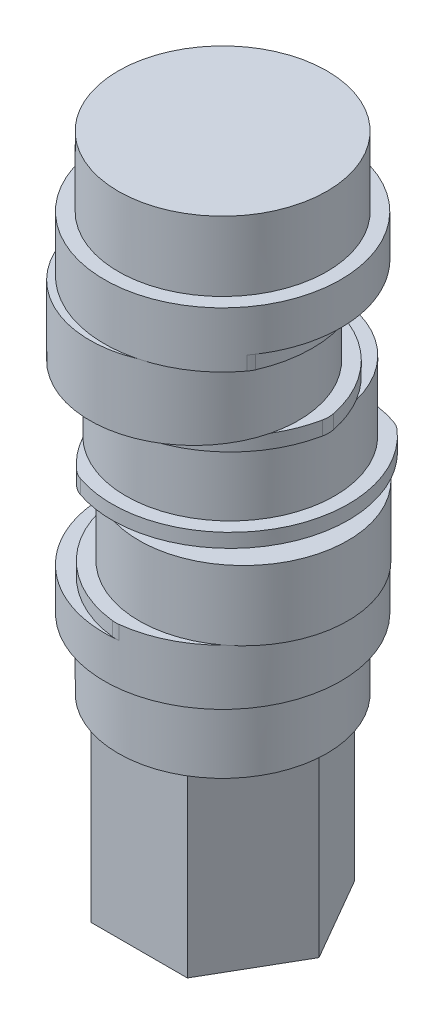
SolidWorks part; units mm, degrees
ref_plane "Front Plane" through (0, 0, 0) normal (0, 0, 1) x (1, 0, 0)
ref_plane "Top Plane" through (0, 0, 0) normal (0, 1, 0) x (1, 0, 0)
ref_plane "Right Plane" through (0, 0, 0) normal (1, 0, 0) x (0, 0, -1)
sketch "Sketch3" plane through (0, 0, 0) normal (0, 1, 0) x (1, 0, 0)
  line L0 (-0.75, 1.299) -> (0, 0) construction
  line L1 (0, 0) -> (-0.75, -1.299) construction
  line L2 (0, 0) -> (1.5, 0) construction
  circle A0 centre (0, 0) radius 1.5 construction
  circle A1 centre (1.5, 0) radius 8.5
  circle A2 centre (-0.75, 1.299) radius 8.5
  circle A3 centre (-0.75, -1.299) radius 8.5
  dimension "D1" = 3
  dimension "D2" = 17
  dimension "D3" = 120
  dimension "D4" = 120
sketch "Sketch4" plane through (0, 0, 0) normal (0, 1, 0) x (1, 0, 0)
  line L1 (-3.4641, 6) -> (-6.9282, 0)
  line L2 (-6.9282, 0) -> (-3.4641, -6)
  line L3 (-3.4641, -6) -> (3.4641, -6)
  line L4 (3.4641, -6) -> (6.9282, 0)
  line L5 (6.9282, 0) -> (3.4641, 6)
  line L6 (3.4641, 6) -> (-3.4641, 6)
  circle A0 centre (0, 0) radius 6 construction
  dimension "D1" = 12
extrude "Boss-Extrude1" add sketch "Sketch4" along normal blind 13
sketch "Sketch5" plane through (0, 13, 0) normal (0, 1, 0) x (1, 0, 0)
  circle A0 centre (0, 0) radius 7.5
  dimension "D1" = 15
extrude "Boss-Extrude2" add sketch "Sketch5" along normal blind 8
sketch "Sketch6" plane through (0, 21, 0) normal (0, 1, 0) x (1, 0, 0)
  circle A0 centre (0, 0) radius 8.5
  circle A1 centre (1.5, 0) radius 8.5
  circle M1 centre (0, 0) radius 7.5
  dimension "D1" = 17
extrude "Boss-Extrude3" add sketch "Sketch6" along normal blind 1 contours A1 M1 | A0 A1 M1 region at (6.1121, 21, 5.5946) region at (0.1719, 21, 0)
sketch "Sketch7" plane through (0, 22, 0) normal (0, 1, 0) x (1, 0, 0)
  circle A0 centre (1.5, 0) radius 7.5
  arc A1 (-4.5833, 5.9366) -> (-4.5833, -5.9366) centre (0, 0) ccw construction
extrude "Boss-Extrude4" add sketch "Sketch7" along normal blind 5
sketch "Sketch8" plane through (0, 27, 0) normal (0, 1, 0) x (1, 0, 0)
  circle A0 centre (1.5, 0) radius 8.5
  circle A1 centre (-0.75, 1.299) radius 8.5
  circle A2 centre (1.5, 0) radius 8.5 construction
  circle M1 centre (1.5, 0) radius 7.5
extrude "Boss-Extrude5" add sketch "Sketch8" along normal blind 1 contours A1 M1 | A1 A0 M1 region at (5.5922, 27, -6.6403) region at (0.8921, 27, -0.3509)
sketch "Sketch9" plane through (0, 28, 0) normal (0, 1, 0) x (1, 0, 0)
  circle A0 centre (-0.75, 1.299) radius 7.5
  arc A1 (-0.6012, -7.1997) -> (6.6845, 5.4195) centre (1.5, 0) ccw construction
extrude "Boss-Extrude6" add sketch "Sketch9" along normal blind 5
sketch "Sketch11" plane through (0, 33, 0) normal (0, 1, 0) x (1, 0, 0)
  circle A0 centre (-0.75, 1.299) radius 8.5
  circle A1 centre (-0.75, -1.299) radius 8.5
  arc A2 (-3.8251, -6.6252) -> (4.5751, 7.9243) centre (-0.75, 1.299) ccw construction
  circle M1 centre (-0.75, 1.299) radius 7.5
extrude "Boss-Extrude7" add sketch "Sketch11" along normal blind 1 contours A1 M1 | A0 A1 M1 region at (-8.5574, 33, -1.5267) region at (-0.75, 33, -0.5972)
sketch "Sketch12" plane through (0, 34, 0) normal (0, 1, 0) x (1, 0, 0)
  circle A0 centre (-0.75, -1.299) radius 7.5
  arc A1 (6.5357, 3.0792) -> (-8.0357, 3.0792) centre (-0.75, 1.299) ccw construction
extrude "Boss-Extrude8" add sketch "Sketch12" along normal blind 5
sketch "Sketch13" plane through (0, 39, 0) normal (0, 1, 0) x (1, 0, 0)
  circle A0 centre (-0.75, -1.299) radius 8.5
  circle A1 centre (0, 0) radius 8.5
  arc A3 (7.6501, 0) -> (-9.1501, 0) centre (-0.75, -1.299) ccw construction
  circle M1 centre (-0.75, -1.299) radius 7.5
extrude "Boss-Extrude9" add sketch "Sketch13" along normal blind 1 contours A1 M1 | A1 A0 M1 region at (7.3307, 39, 3.0859) region at (-0.664, 39, 1.1501)
sketch "Sketch14" plane through (0, 40, 0) normal (0, 1, 0) x (1, 0, 0)
  circle A0 centre (0, 0) radius 7.5
  arc A1 (6.5357, 3.0792) -> (-8.0357, 3.0792) centre (-0.75, 1.299) ccw construction
extrude "Boss-Extrude10" add sketch "Sketch14" along normal blind 8
fillet "Fillet1" radius 2 8 edges at (0.75, 21.5, -8.4668) (0.75, 21.5, 8.4668) (-3.8251, 27.5, 6.6252) (4.5751, 27.5, -7.9243) (7.6501, 33.5, 0) (-9.1501, 33.5, 0) (-7.7075, 39.5, -3.5839) (6.9575, 39.5, 4.8829)
sketch "Sketch15" plane through (0, 21, 0) normal (0, -1, 0) x (1, 0, 0)
  circle A0 centre (0, 0) radius 8.5
  dimension "D1" = 17
extrude "Boss-Extrude11" add sketch "Sketch15" along normal blind 3
sketch "Sketch16" plane through (0, 40, 0) normal (0, -1, 0) x (1, 0, 0)
  circle A0 centre (0, 0) radius 8.5
  dimension "D1" = 17
extrude "Boss-Extrude12" add sketch "Sketch16" against normal blind 3
equation "\"N_pin\"= 24"
equation "\"R_pin\"= 60"
equation "\"d_pin\"= 13"
equation "\"e\"= 1.5"
equation "\"t_disk\"= 5"
equation "\"N_outpin\"= 8"
equation "\"R_outpin\"= 34"
equation "\"d_outpin\"= 13"
equation "\"N_lobes\"= \"N_pin\" - 1"
equation "\"d_outhole\"= \"d_outpin\" + 2 * \"e\""
equation "\"ratio\"= \"N_lobes\""
equation "\"d_center\"= 24"
equation "\"a_hole1\"= 0 / \"N_lobes\""
equation "\"a_hole2\"= 360 / \"N_disk\" / \"N_lobes\""
equation "\"a_hole3\"= 720 / \"N_disk\" / \"N_lobes\""
equation "\"N_disk\"= 3"
equation "\"t_gap\"= 1"
equation "\"L_stack\"= \"N_disk\" * \"t_disk\" + (\"N_disk\" - 1) * \"t_gap\""
equation "\"d_pinshaft\"= 6"
equation "\"d_ecc\"= 15"
equation "\"d_outbrg\"= 47"
equation "\"w_outbrg\"= 7"
equation "\"d_outshaft\"= 35"
equation "\"w_brg\"= 5"
equation "\"D1@Boss-Extrude5\"=\"t_gap\""
equation "\"D1@Boss-Extrude7\"=\"t_gap\""
equation "\"c_run\"= 0.5"
equation "\"c_ax\"= \"t_gap\""
equation "\"D_pocket\"= 2 * \"R_pin\" + \"d_pin\" + 2 * \"c_run\""
equation "\"h_pocket\"= \"L_stack\" + 2 * \"c_ax\""
equation "\"t_floor\"= 8"
equation "\"d_insert\"= 5.6"
equation "\"N_bolt\"= 8"
equation "\"R_bolt\"= \"D_pocket\" / 2 + 2 + \"d_insert\" / 2"
equation "\"D_housing\"= 2 * (\"R_bolt\" + \"d_insert\" / 2 + 2.5)"
equation "\"D1@Boss-Extrude2\"=\"t_floor\""
equation "\"D1@Sketch5\"=\"d_ecc\""
equation "\"D1@Boss-Extrude10\"=\"t_floor\""
equation "\"D1@Boss-Extrude8\"=\"w_brg\""
equation "\"D1@Boss-Extrude6\"=\"w_brg\""
equation "\"D1@Boss-Extrude4\"=\"w_brg\""
equation "\"D1@Sketch6\"=\"d_ecc\"+2"
equation "\"D1@Sketch15\"=\"d_ecc\"+2"
equation "\"D1@Boss-Extrude11\"=\"t_floor\"-\"w_brg\""
equation "\"D1@Boss-Extrude3\"=\"t_gap\""
equation "\"D1@Boss-Extrude9\"=\"t_gap\""
equation "\"D1@Sketch16\"=\"d_ecc\"+2"
equation "\"D1@Boss-Extrude12\"=\"t_floor\"-\"w_brg\""
